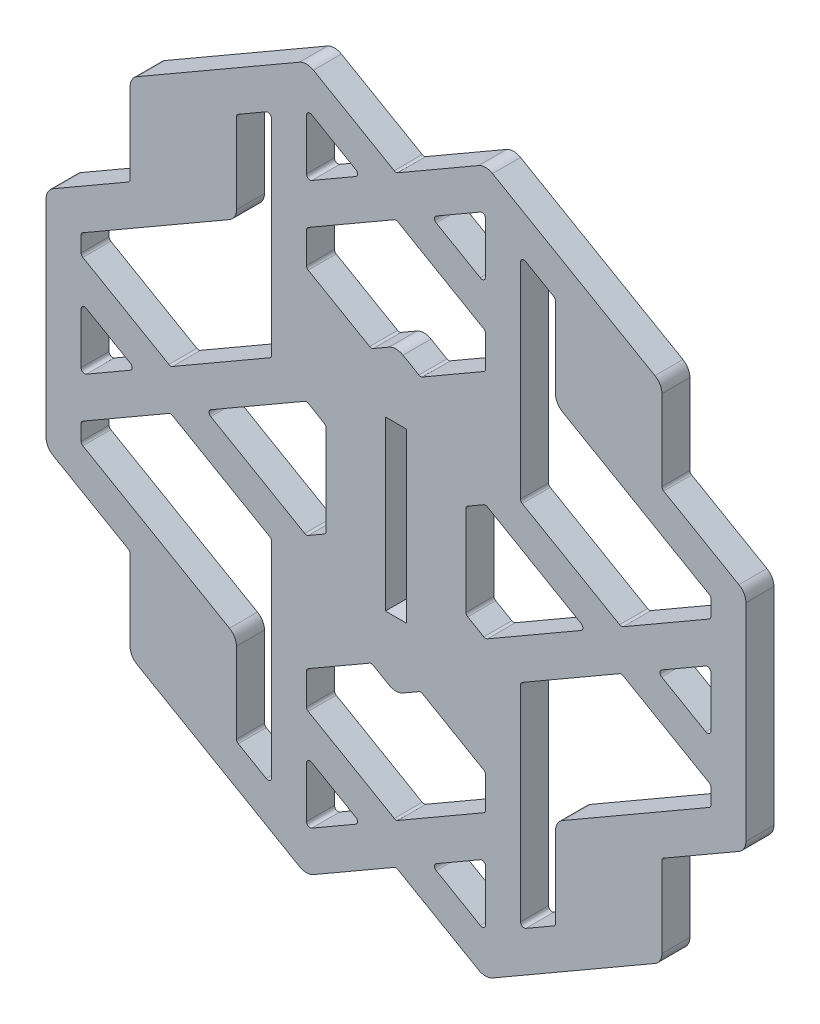
SolidWorks part; units mm, degrees
ref_plane "前视基准面" through (0, 0, 0) normal (0, 0, 1) x (1, 0, 0)
ref_plane "上视基准面" through (0, 0, 0) normal (0, 1, 0) x (1, 0, 0)
ref_plane "右视基准面" through (0, 0, 0) normal (1, 0, 0) x (0, 0, -1)
sketch "草图1" plane through (0, 0, 0) normal (0, 0, 1) x (1, 0, 0)
  line L0 (0, 1023.2814) -> (0, 21.4808) construction
  line L3 (-5.1371, 0) -> (4.4095, 0) construction
  line L13 (-38, -22.8564) -> (-38, -35.7957)
  line L14 (-10, -6.7073) -> (-10, 6.7073)
  line L16 (-38, -35.7957) -> (-12.7942, -50.3483)
  line L17 (-12.7942, -44.5748) -> (-12.7942, -35.5748)
  line L18 (-38, -22.8564) -> (-50, -15.9282)
  line L19 (-50, -15.9282) -> (-50, -13.1603)
  line L20 (-27.2058, 0) -> (-12.7942, -8.3205)
  line L23 (10, -6.7073) -> (10, 6.7073)
  line L25 (-3.5215, -19.4476) -> (-12.7942, -24.8013)
  line L26 (-10, -6.7073) -> (-12.7942, -8.3205)
  line L27 (10, -6.7073) -> (12.7942, -8.3205)
  line L28 (3.5215, -19.4476) -> (12.7942, -24.8013)
  line L29 (12.7942, -44.5748) -> (12.7942, -35.5748)
  line L30 (38, -35.7957) -> (12.7942, -50.3483)
  line L31 (38, -22.8564) -> (38, -35.7957)
  line L32 (38, -22.8564) -> (50, -15.9282)
  line L33 (50, -15.9282) -> (50, -13.1603)
  line L34 (27.2058, 0) -> (12.7942, -8.3205)
  line L35 (10, 6.7073) -> (12.7942, 8.3205)
  line L36 (-10, 6.7073) -> (-12.7942, 8.3205)
  line L37 (3.5215, 19.4476) -> (12.7942, 24.8013)
  line L38 (-3.5215, 19.4476) -> (-12.7942, 24.8013)
  line L39 (12.7942, 44.5748) -> (12.7942, 35.5748)
  line L40 (38, 35.7957) -> (12.7942, 50.3483)
  line L41 (38, 22.8564) -> (38, 35.7957)
  line L42 (38, 22.8564) -> (50, 15.9282)
  line L43 (50, 15.9282) -> (50, 13.1603)
  line L44 (27.2058, 0) -> (12.7942, 8.3205)
  line L45 (-12.7942, 44.5748) -> (-12.7942, 35.5748)
  line L46 (-38, 35.7957) -> (-12.7942, 50.3483)
  line L47 (-38, 22.8564) -> (-38, 35.7957)
  line L48 (-38, 22.8564) -> (-50, 15.9282)
  line L49 (-50, 15.9282) -> (-50, 13.1603)
  line L50 (-27.2058, 0) -> (-12.7942, 8.3205)
  line L51 (-12.7942, -50.3483) -> (0, -42.9615)
  line L52 (-12.7942, -44.5748) -> (-5, -40.0748)
  line L53 (-5, -40.0748) -> (-12.7942, -35.5748)
  line L54 (0, -37.188) -> (-12.7942, -29.8013)
  line L55 (12.7942, -50.3483) -> (0, -42.9615)
  line L56 (12.7942, -44.5748) -> (5, -40.0748)
  line L57 (5, -40.0748) -> (12.7942, -35.5748)
  line L58 (0, -37.188) -> (12.7942, -29.8013)
  line L59 (-12.7942, -35.5748) -> (-12.7942, -29.8013) construction
  line L60 (-12.7942, -29.8013) -> (-12.7942, -24.8013)
  line L61 (-12.7942, -50.3483) -> (-12.7942, -44.5748) construction
  line L62 (12.7942, -35.5748) -> (12.7942, -29.8013) construction
  line L63 (12.7942, -29.8013) -> (12.7942, -24.8013)
  line L64 (12.7942, -50.3483) -> (12.7942, -44.5748) construction
  line L67 (-50, 13.1603) -> (-50, -13.1603)
  line L68 (-45, 4.5) -> (-45, -4.5)
  line L69 (-45, -4.5) -> (-37.2058, 0)
  line L70 (-37.2058, 0) -> (-45, 4.5)
  line L71 (45, -4.5) -> (37.2058, 0)
  line L72 (45, 4.5) -> (45, -4.5)
  line L73 (37.2058, 0) -> (45, 4.5)
  line L74 (50, 13.1603) -> (50, -13.1603)
  line L75 (-50, -13.1603) -> (-27.2058, 0) construction
  line L76 (-50, 13.1603) -> (-27.2058, 0) construction
  line L77 (50, 13.1603) -> (27.2058, 0) construction
  line L78 (50, -13.1603) -> (27.2058, 0) construction
  line L79 (-32.2058, 2.8868) -> (-17.7942, 11.2073)
  line L80 (-17.7942, 11.2073) -> (-17.7942, 41.688)
  line L81 (-17.7942, 41.688) -> (-22.7942, 38.8013)
  line L82 (-22.7942, 38.8013) -> (-22.7942, 25.862)
  line L83 (-22.7942, 25.862) -> (-45, 13.0415)
  line L84 (-45, 13.0415) -> (-45, 10.2735)
  line L85 (-45, 10.2735) -> (-32.2058, 2.8868)
  line L86 (12.7942, 44.5748) -> (5, 40.0748)
  line L87 (5, 40.0748) -> (12.7942, 35.5748)
  line L88 (0, 37.188) -> (12.7942, 29.8013)
  line L89 (0, 37.188) -> (-12.7942, 29.8013)
  line L90 (-5, 40.0748) -> (-12.7942, 35.5748)
  line L91 (-12.7942, 44.5748) -> (-5, 40.0748)
  line L92 (-12.7942, 50.3483) -> (0, 42.9615)
  line L93 (-12.7942, 50.3483) -> (-12.7942, 44.5748) construction
  line L94 (-12.7942, 35.5748) -> (-12.7942, 29.8013) construction
  line L95 (-12.7942, 29.8013) -> (-12.7942, 24.8013)
  line L96 (12.7942, 35.5748) -> (12.7942, 29.8013) construction
  line L97 (12.7942, 29.8013) -> (12.7942, 24.8013)
  line L98 (12.7942, 50.3483) -> (12.7942, 44.5748) construction
  line L99 (12.7942, 50.3483) -> (0, 42.9615)
  line L100 (45, 13.0415) -> (45, 10.2735)
  line L101 (22.7942, 25.862) -> (45, 13.0415)
  line L102 (22.7942, 38.8013) -> (22.7942, 25.862)
  line L103 (17.7942, 41.688) -> (22.7942, 38.8013)
  line L104 (17.7942, 11.2073) -> (17.7942, 41.688)
  line L105 (32.2058, 2.8868) -> (17.7942, 11.2073)
  line L106 (45, 10.2735) -> (32.2058, 2.8868)
  line L107 (22.7942, -25.862) -> (45, -13.0415)
  line L108 (22.7942, -38.8013) -> (22.7942, -25.862)
  line L109 (17.7942, -41.688) -> (22.7942, -38.8013)
  line L110 (17.7942, -11.2073) -> (17.7942, -41.688)
  line L111 (32.2058, -2.8868) -> (17.7942, -11.2073)
  line L112 (45, -10.2735) -> (32.2058, -2.8868)
  line L113 (45, -13.0415) -> (45, -10.2735)
  line L114 (-45, -13.0415) -> (-45, -10.2735)
  line L115 (-22.7942, -25.862) -> (-45, -13.0415)
  line L116 (-22.7942, -38.8013) -> (-22.7942, -25.862)
  line L117 (-17.7942, -41.688) -> (-22.7942, -38.8013)
  line L118 (-17.7942, -11.2073) -> (-17.7942, -41.688)
  line L119 (-32.2058, -2.8868) -> (-17.7942, -11.2073)
  line L120 (-45, -10.2735) -> (-32.2058, -2.8868)
  line L121 (-3.5215, 19.4476) -> (0, 21.4808)
  line L123 (3.5215, 19.4476) -> (0, 21.4808)
  line L124 (3.5215, -19.4476) -> (0, -21.4808)
  line L125 (-3.5215, -19.4476) -> (0, -21.4808)
  line L126 (0, 17.4145) -> (-3.5215, 19.4476) construction
  line L127 (0, 21.4808) -> (0, 17.4145) construction
  line L128 (0, 17.4145) -> (0, -17.4145) construction
  line L129 (0, 17.4145) -> (3.5215, 19.4476) construction
  line L130 (0, -17.4145) -> (-3.5215, -19.4476) construction
  line L131 (0, -17.4145) -> (0, -21.4808) construction
  line L132 (0, -21.4808) -> (0, -1032.2044) construction
  line L133 (0, -17.4145) -> (3.5215, -19.4476) construction
  dimension "D1" = 30
  dimension "D2" = 100
  dimension "D3" = 76
  dimension "D4" = 9
  dimension "D5" = 9
  dimension "D6" = 5
  dimension "D7" = 5
  dimension "D8" = 5
  dimension "D9" = 100
  dimension "D10" = 5
  dimension "D11" = 5
  dimension "D12" = 5
  dimension "D13" = 76
  dimension "D14" = 20
  dimension "D15" = 5
  dimension "D16" = 5
  dimension "D17" = 34.829
extrude "凸台-拉伸1" add sketch "草图1" along normal blind 4
sketch "草图2" plane through (0, 0, 0) normal (0, 0, 1) x (1, 0, 0)
  line L0 (-12.7164, 0) -> (-4.9635, 0) construction
  line L1 (-1.51, 12.01) -> (1.51, 12.01)
  line L2 (-1.51, 12.01) -> (-1.51, -12.01)
  line L3 (-1.51, -12.01) -> (1.51, -12.01)
  line L4 (1.51, 12.01) -> (1.51, -12.01)
  line L5 (0, 12.8028) -> (0, 10.1895) construction
  dimension "D1" = 24.02
  dimension "D2" = 3.02
extrude "切除-拉伸1" cut sketch "草图2" along normal blind 4
fillet "圆角1" radius 2 18 edges at (38, -35.7957, 2) (50, -15.9282, 2) (50, 15.9282, 2) (38, 35.7957, 2) (12.7942, 50.3483, 2) (-12.7942, 50.3483, 2) (12.7942, -50.3483, 2) (-12.7942, -50.3483, 2) (-38, 35.7957, 2) (-50, 15.9282, 2) (-38, -35.7957, 2) (-50, -15.9282, 2) (-22.7942, -25.862, 2) (22.7942, -25.862, 2) (22.7942, 25.862, 2) (-22.7942, 25.862, 2) (0, -21.4808, 2) (0, 21.4808, 2)
fillet "圆角2" radius 0.5 72 edges at (3.5215, 19.4476, 2) (-3.5215, 19.4476, 2) (12.7942, 29.8013, 2) (12.7942, 24.8013, 2) (-12.7942, 24.8013, 2) (-12.7942, 29.8013, 2) (0, 37.188, 2) (-12.7942, 35.5748, 2) (-5, 40.0748, 2) (-12.7942, 44.5748, 2) (45, -13.0415, 2) (45, -10.2735, 2) (32.2058, -2.8868, 2) (17.7942, -11.2073, 2) (22.7942, -38.8013, 2) (17.7942, -41.688, 2) (12.7942, -44.5748, 2) (12.7942, -35.5748, 2) (5, -40.0748, 2) (12.7942, -29.8013, 2) (12.7942, -24.8013, 2) (0, -37.188, 2) (3.5215, -19.4476, 2) (-3.5215, -19.4476, 2) (-12.7942, -24.8013, 2) (-12.7942, -29.8013, 2) (-5, -40.0748, 2) (-12.7942, -35.5748, 2) (-12.7942, -44.5748, 2) (-22.7942, -38.8013, 2) (-17.7942, -41.688, 2) (-17.7942, -11.2073, 2) (-32.2058, -2.8868, 2) (-45, -10.2735, 2) (-45, -13.0415, 2) (-10, 6.7073, 2) (-12.7942, 8.3205, 2) (-27.2058, 0, 2) (-12.7942, -8.3205, 2) (-10, -6.7073, 2) (-45, 4.5, 2) (-45, -4.5, 2) (-37.2058, 0, 2) (-22.7942, 38.8013, 2) (-45, 13.0415, 2) (-45, 10.2735, 2) (-32.2058, 2.8868, 2) (-17.7942, 11.2073, 2) (-17.7942, 41.688, 2) (10, -6.7073, 2) (12.7942, -8.3205, 2) (27.2058, 0, 2) (10, 6.7073, 2) (12.7942, 8.3205, 2) (37.2058, 0, 2) (45, -4.5, 2) (45, 4.5, 2) (32.2058, 2.8868, 2) (17.7942, 11.2073, 2) (45, 10.2735, 2) (45, 13.0415, 2) (22.7942, 38.8013, 2) (17.7942, 41.688, 2) (12.7942, 35.5748, 2) (12.7942, 44.5748, 2) (5, 40.0748, 2) (-38, -22.8564, 2) (0, -42.9615, 2) (38, -22.8564, 2) (38, 22.8564, 2) (0, 42.9615, 2) (-38, 22.8564, 2)
